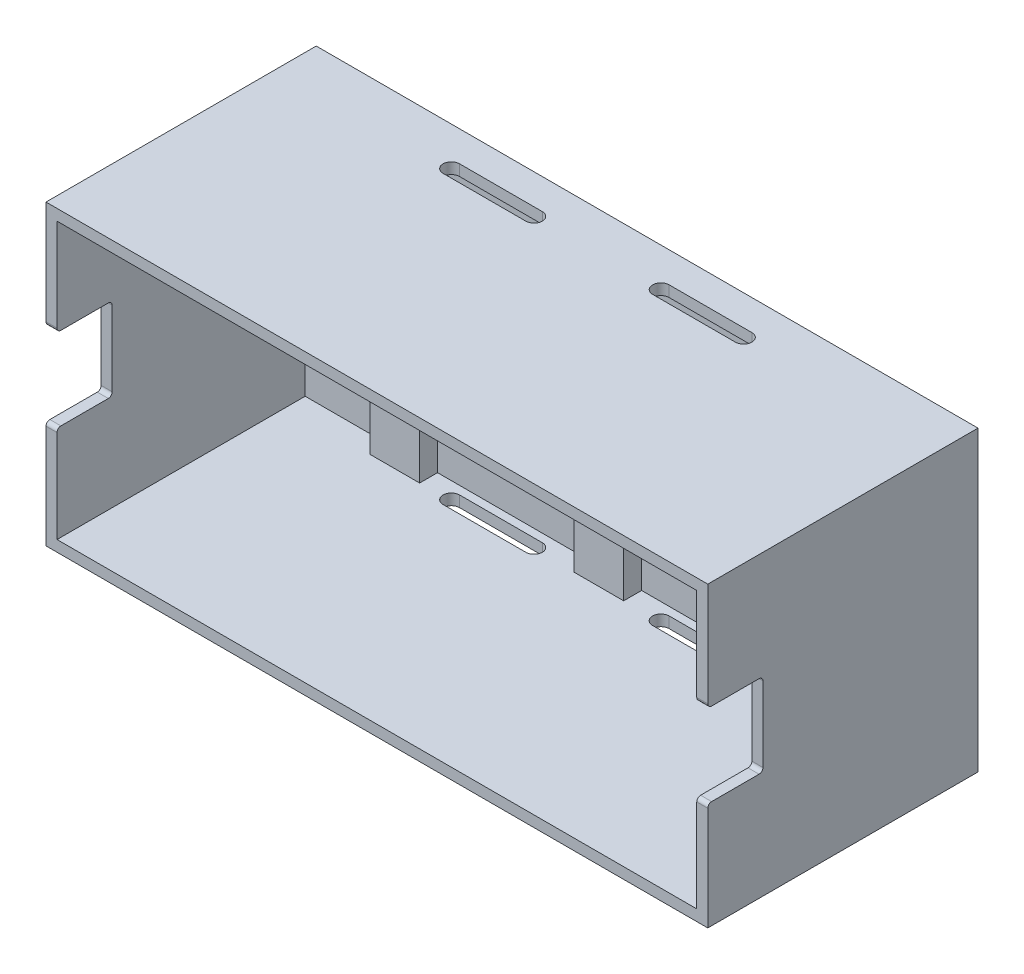
SolidWorks part; units mm, degrees
ref_plane "Front" through (0, 0, 0) normal (0, 0, 1) x (1, 0, 0)
ref_plane "Top" through (0, 0, 0) normal (0, 1, 0) x (1, 0, 0)
ref_plane "Right" through (0, 0, 0) normal (1, 0, 0) x (0, 0, -1)
sketch "Sketch1" plane through (0, 0, 0) normal (0, 0, 1) x (1, 0, 0)
  line L1 (-80.7473, 47) -> (39.2527, 47)
  line L2 (-80.7473, 47) -> (-80.7473, -7)
  line L3 (-80.7473, -7) -> (39.2527, -7)
  line L4 (39.2527, 47) -> (39.2527, -7)
  dimension "D1" = 54
  dimension "D2" = 120
extrude "Boss-Extrude1" add sketch "Sketch1" along normal blind 4 contours L1 L4 L3 L2
sketch "Sketch2" plane through (0, 0, 4) normal (0, 0, 1) x (1, 0, 0)
  line L1 (-80.7473, 47) -> (39.2527, 47)
  line L2 (-80.7473, 47) -> (-80.7473, -7)
  line L3 (-80.7473, -7) -> (39.2527, -7)
  line L4 (39.2527, 47) -> (39.2527, -7)
  line L5 (-78.7473, 45) -> (37.2527, 45)
  line L6 (-78.7473, 45) -> (-78.7473, -5)
  line L7 (-78.7473, -5) -> (37.2527, -5)
  line L8 (37.2527, 45) -> (37.2527, -5)
  dimension "D1" = 2
  dimension "D2" = 2
  dimension "D3" = 2
  dimension "D4" = 2
extrude "Boss-Extrude2" add sketch "Sketch2" along normal blind 45
sketch "Sketch3" plane through (0, 0, 4) normal (0, 0, 1) x (1, 0, 0)
  line L0 (37.2527, 45) -> (-78.7473, 45) construction
  line L1 (-63.7473, 45) -> (-54.7473, 45)
  line L2 (-63.7473, 45) -> (-63.7473, -5)
  line L3 (-63.7473, -5) -> (-54.7473, -5)
  line L4 (-54.7473, 45) -> (-54.7473, -5)
  line L5 (-78.7473, -5) -> (37.2527, -5) construction
  line L6 (-78.7473, -5) -> (37.2527, -5) construction
  line L7 (-26.7473, 45) -> (-17.7473, 45)
  line L8 (-26.7473, 45) -> (-26.7473, -5)
  line L9 (-26.7473, -5) -> (-17.7473, -5)
  line L10 (-17.7473, 45) -> (-17.7473, -5)
  line L11 (37.2527, 45) -> (-78.7473, 45) construction
  line L12 (10.2527, 45) -> (19.2527, 45)
  line L13 (10.2527, 45) -> (10.2527, -5)
  line L14 (10.2527, -5) -> (19.2527, -5)
  line L15 (19.2527, 45) -> (19.2527, -5)
  line L16 (37.2527, -5) -> (37.2527, 45) construction
  dimension "D1" = 9
  dimension "D2" = 9
  dimension "D3" = 9
  dimension "D4" = 18
  dimension "D5" = 28
  dimension "D6" = 28
extrude "Boss-Extrude3" add sketch "Sketch3" along normal blind 3.25
sketch "Sketch4" plane through (0, 0, 4) normal (0, 0, 1) x (1, 0, 0)
  line L2 (37.2527, 45) -> (-78.7473, 45) construction
  line L3 (37.2527, 45) -> (19.2527, 45) construction
  circle A0 centre (-4.7425, 39.5) radius 1.65
  circle A1 centre (-42.2054, 39.5) radius 1.65
  circle A3 centre (-72.6736, 39.5) radius 1.65
  circle A4 centre (29.2823, 39.5) radius 1.65
  dimension "D1" = 3.3
  dimension "D2" = 5.5
  dimension "D3" = 5.5
  dimension "D4" = 5.5
  dimension "D5" = 5.5
extrude "Cut-Extrude5" cut sketch "Sketch4" against normal blind 14
sketch "Sketch5" plane through (39.2527, 0, 0) normal (1, 0, 0) x (0, 0, -1)
  line L0 (-49, 27.5) -> (-39, 27.5)
  line L1 (-49, -7) -> (-49, 47) construction
  line L2 (-39, 27.5) -> (-39, 12.5)
  line L3 (-39, 12.5) -> (-49, 12.5)
  line L4 (-49, 47) -> (0, 47) construction
  line L8 (-49, 27.5) -> (-49, 12.5)
  dimension "D1" = 10
  dimension "D2" = 15
  dimension "D3" = 19.5
extrude "Cut-Extrude7" cut sketch "Sketch5" against normal through all contours L8 L3 L2 L0
fillet "Fillet1" radius 0.7 1 edges at (38.2527, 12.5, 39)
fillet "Fillet2" radius 0.7 1 edges at (38.2527, 27.5, 39)
fillet "Fillet3" radius 0.7 1 edges at (-79.7473, 12.5, 39)
fillet "Fillet4" radius 0.7 1 edges at (-79.7473, 27.5, 39)
fillet "Fillet5" radius 0.7 1 edges at (-79.7473, 12.5, 49)
fillet "Fillet6" radius 0.7 1 edges at (-79.7473, 27.5, 49)
fillet "Fillet7" radius 0.7 1 edges at (38.2527, 12.5, 49)
fillet "Fillet8" radius 0.7 1 edges at (38.2527, 27.5, 49)
sketch "Sketch6" plane through (0, -5, 0) normal (0, 1, 0) x (1, 0, 0)
  line L0 (-49.2473, -7) -> (-34.2473, -7) construction
  line L1 (-49.2473, -5.5) -> (-34.2473, -5.5)
  line L2 (-49.2473, -8.5) -> (-34.2473, -8.5)
  line L3 (-11.2473, -7) -> (3.7527, -7) construction
  line L4 (-11.2473, -5.5) -> (3.7527, -5.5)
  line L5 (-11.2473, -8.5) -> (3.7527, -8.5)
  line L6 (-78.7473, -4) -> (-63.7473, -4) construction
  line L7 (-78.7473, -49) -> (-78.7473, -4) construction
  line L8 (37.2527, -49) -> (37.2527, -4) construction
  arc A0 (-49.2473, -5.5) -> (-49.2473, -8.5) centre (-49.2473, -7) ccw
  arc A1 (-34.2473, -8.5) -> (-34.2473, -5.5) centre (-34.2473, -7) ccw
  arc A2 (-11.2473, -5.5) -> (-11.2473, -8.5) centre (-11.2473, -7) ccw
  arc A3 (3.7527, -8.5) -> (3.7527, -5.5) centre (3.7527, -7) ccw
  point P2 (-41.7473, -7)
  point P7 (-3.7473, -7)
  point P14 (0, 0)
  dimension "D1" = 15
  dimension "D2" = 3
  dimension "D3" = 3
  dimension "D4" = 37
  dimension "D5" = 41
extrude "Cut-Extrude8" cut sketch "Sketch6" against normal through all both and the other way through all
